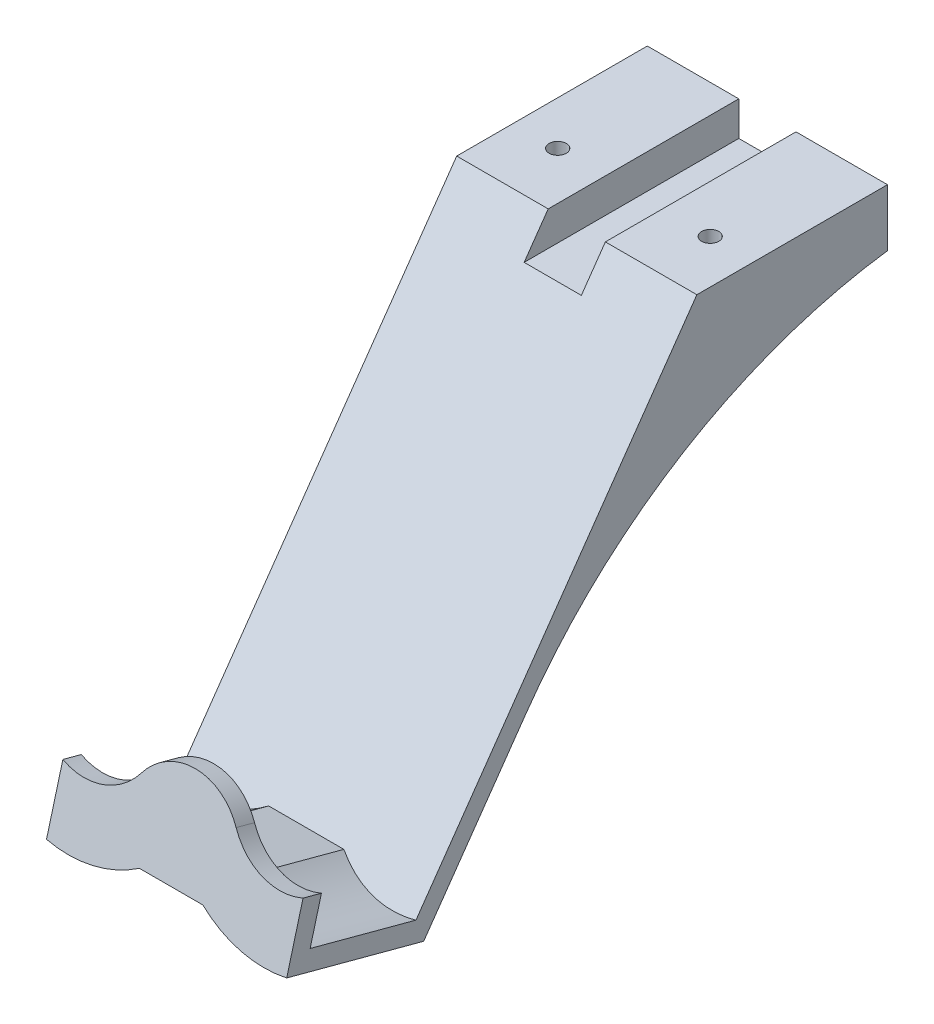
SolidWorks part; units mm, degrees
ref_plane "Front Plane" through (0, 0, 0) normal (0, 0, 1) x (1, 0, 0)
ref_plane "Top Plane" through (0, 0, 0) normal (0, 1, 0) x (1, 0, 0)
ref_plane "Right Plane" through (0, 0, 0) normal (1, 0, 0) x (0, 0, -1)
sketch "Sketch1" plane through (0, 0, 0) normal (1, 0, 0) x (0, 0, -1)
  line L0 (0, 0) -> (-74.9222, -107)
  line L1 (-74.9222, -107) -> (-101.9681, -99.7531)
  line L2 (-101.9681, -99.7531) -> (-94.7212, -72.7071)
  line L3 (-412.5598, 134.4346) -> (316.9288, 134.4346) construction
  line L4 (0, 0) -> (34.7282, 0) construction
  line L5 (-94.7212, -72.7071) -> (-66.4005, -80.2957)
  line L6 (-66.4005, -80.2957) -> (-8.1685, 5.7197)
  line L7 (-8.1685, 5.7197) -> (0, 0)
  dimension "D1" = 107
  dimension "D2" = 125
  dimension "D3" = 110
  dimension "D4" = 28
  dimension "D5" = 28
extrude "Boss-Extrude1" add sketch "Sketch1" along normal mid plane 63
sketch "Sketch2" plane through (0, 18.8098, 70.1993) normal (0, 0.2588, 0.9659) x (1, 0, 0)
  line L0 (-95.5431, -163.633) -> (189.7902, -163.633) construction
  line L1 (31.5, -94.7454) -> (31.5, -122.7454) construction
  line L2 (-31.5, -94.7454) -> (-31.5, -122.7454) construction
  line L3 (31.5, -94.7454) -> (-31.5, -94.7454) construction
  line L4 (31.5, -94.7454) -> (31.5, -109.2454)
  line L5 (-31.5, -94.7454) -> (-31.5, -109.2454)
  line L6 (31.5, -94.7454) -> (-31.5, -94.7454)
  line L7 (0, -94.7454) -> (0, -111.7454) construction
  arc A0 (-31.5, -109.2454) -> (-12.4157, -103.3281) centre (-25.6591, -94.3496) ccw
  arc A1 (-12.4157, -103.3281) -> (12.4157, -103.3281) centre (0, -111.7454) cw
  arc A2 (31.5, -109.2454) -> (12.4157, -103.3281) centre (25.6591, -94.3496) cw
  point P13 (-11.1172, -102.2824)
  point P14 (0, -107.8058)
  point P15 (0, -113.5427)
  point P16 (0, -112.5149)
  point P20 (12.2852, -102.9366)
  dimension "D1" = 15
  dimension "D2" = 16
  dimension "D3" = 17
  dimension "D4" = 14.5
extrude "Cut-Extrude1" cut sketch "Sketch2" against normal up to surface (24.2993 mm away) up to face at (0, -37.288, 37.2845)
sketch "Sketch3" plane through (0, 18.8098, 70.1993) normal (0, 0.2588, 0.9659) x (1, 0, 0)
  line L0 (-170.5741, -239.4978) -> (114.7593, -239.4978) construction
  line L1 (31.5, -109.2454) -> (31.5, -122.7454) construction
  line L2 (-31.5, -109.2454) -> (-31.5, -122.7454) construction
  line L3 (31.5, -122.7454) -> (-31.5, -122.7454) construction
  line L4 (31.5, -120.7102) -> (31.5, -122.7454)
  line L5 (-31.5, -120.7102) -> (-31.5, -122.7454)
  line L6 (31.5, -122.7454) -> (-31.5, -122.7454)
  line L7 (0, -122.7454) -> (0, -116.2454) construction
  line L8 (-9.8611, -116.2454) -> (9.8611, -116.2454)
  arc A0 (-31.5, -120.7102) -> (-9.8611, -116.2454) centre (-25.6591, -94.3496) ccw
  arc A2 (-31.5, -109.2454) -> (-12.4157, -103.3281) centre (-25.6591, -94.3496) ccw construction
  arc A3 (31.5, -120.7102) -> (9.8611, -116.2454) centre (25.6591, -94.3496) cw
  point P11 (0, -116.2454)
  point P14 (0, 0)
  point P15 (-11.0206, -115.9939)
  point P16 (-31.5, -120.2996)
  dimension "D2" = 27
  dimension "D1" = 6.5
extrude "Cut-Extrude2" cut sketch "Sketch3" against normal blind 63
shell "Shell1" thickness 5 removed face at (0, 2.8598, 4.0843) removed face at (0, -58.3822, 51.5651) removed face at (31.5, -62.8348, 59.4611) removed face at (-31.5, -62.8348, 59.4611) removed face at (-21.4392, -88.673, 86.1905) removed face at (0, -81.3754, 82.8152) removed face at (21.4392, -88.673, 86.1905) outward yes
sketch "Sketch4" plane through (0, 0, 0) normal (1, 0, 0) x (0, 0, -1)
  line L0 (0, 0) -> (50, 0)
  line L1 (50, 0) -> (50, -15)
  line L2 (0, 0) -> (-49.0145, -70)
  line L3 (-73.68, -105.2259) -> (0, 0) construction
  line L4 (-49.0145, -70) -> (-44.9188, -72.8679)
  line L5 (-71.6545, -111.0504) -> (4.0958, -2.8679) construction
  line L7 (-44.9188, -72.8679) -> (-37.5792, -62.3859) construction
  arc A1 (-44.9188, -72.8679) -> (50, -15) centre (68.6698, -152.4035) cw
  point P11 (38.7274, -8.148)
  point P14 (35.2109, -7.5161)
  point P15 (36.7461, -7.5161)
  point P16 (49.7685, -10)
  point P17 (43.9306, -10)
  point P18 (58.3983, -10)
  dimension "D2" = 50
  dimension "D1" = 70
  dimension "D3" = 15
extrude "Boss-Extrude2" add sketch "Sketch4" along normal mid plane 63
sketch "Sketch5" plane through (0, 0, -50) normal (0, 0, -1) x (-1, 0, 0)
  line L0 (-31.5, 0) -> (31.5, 0) construction
  line L1 (-7.5, 0) -> (7.5, 0)
  line L2 (-7.5, 0) -> (-7.5, -9)
  line L3 (-7.5, -9) -> (7.5, -9)
  line L4 (7.5, 0) -> (7.5, -9)
  point P6 (0, 0)
  dimension "D1" = 15
  dimension "D2" = 9
extrude "Cut-Extrude3" cut sketch "Sketch5" against normal blind 63
ref_plane "Plane1" through (0, -40, 0) normal (0, 1, 0) x (1, 0, 0)
sketch "Sketch6" plane through (0, -40, 0) normal (0, 1, 0) x (1, 0, 0)
  line L0 (0, 0) -> (0, 15) construction
  line L1 (-20, 15) -> (20, 15) construction
  circle A0 centre (20, 15) radius 5
  circle A1 centre (-20, 15) radius 5
  point P6 (0, 15)
  point P7 (-20, 15)
  point P8 (20, 15)
  dimension "D3" = 10
  dimension "D1" = 15
  dimension "D2" = 40
extrude "Cut-Extrude4" cut sketch "Sketch6" along normal blind 30
hole_wizard "CSK for M4 Countersunk Flat Head Screw1" positions "3DSketch1" profile "Sketch7" countersink size "M4" standard "ISO"
sketch3d "3DSketch1"
  line L0 (-20, -10, -15) -> (-20, -26.7606, -15) construction
  line L1 (20, -10, -15) -> (20, -26.7606, -15) construction
  point P0 (-20, -10, -15)
  point P4 (20, -10, -15)
sketch "Sketch7" plane through (-20, -10, -15) normal (1, 0, 0) x (0, 0, -1)
  line L0 (0, 0) -> (0, 16.5519)
  line L1 (0, 16.5519) -> (2.25, 15.2)
  line L2 (2.25, 15.2) -> (2.25, 2.45)
  line L3 (2.25, 2.45) -> (4.7, 0)
  line L5 (4.7, 0) -> (0, 0)
  line L6 (-2.25, 2.45) -> (-4.7, 0) construction
  line L10 (0, 16.5519) -> (-2.25, 15.2) construction
  line L11 (0, -6.35) -> (0, 107.95) construction
  dimension "Hole Dia." = 4.5
  dimension "Hole Depth" = 15.2
  dimension "Near C'Sink Dia." = 9.4
  dimension "Near C'Sink Angle" = 90
  dimension "Drill Angle" = 118
